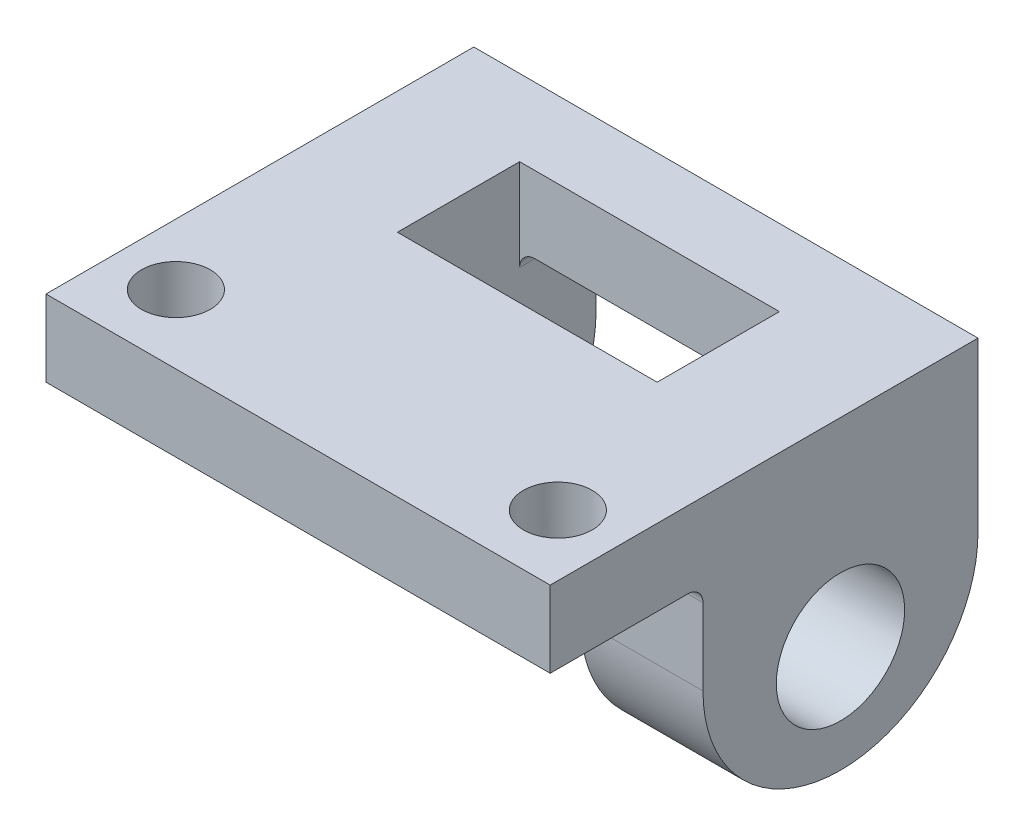
SolidWorks part; units mm, degrees
ref_plane "前视基准面" through (0, 0, 0) normal (0, 0, 1) x (1, 0, 0)
ref_plane "上视基准面" through (0, 0, 0) normal (0, 1, 0) x (1, 0, 0)
ref_plane "右视基准面" through (0, 0, 0) normal (1, 0, 0) x (0, 0, -1)
sketch "草图1" plane through (0, 0, 0) normal (0, 1, 0) x (1, 0, 0)
  line L0 (-18.5322, 0) -> (26.7717, 0) construction
  line L1 (-8.5, 4) -> (8.5, 4)
  line L2 (-8.5, 4) -> (-8.5, -4)
  line L3 (-8.5, -4) -> (8.5, -4)
  line L4 (8.5, 4) -> (8.5, -4)
  line L5 (0, 17.1481) -> (0, -22.7749) construction
  line L7 (-16.5, 9) -> (16.5, 9)
  line L8 (-16.5, 9) -> (-16.5, -19)
  line L9 (-16.5, -19) -> (16.5, -19)
  line L10 (16.5, 9) -> (16.5, -19)
  dimension "D1" = 8
  dimension "D2" = 17
  dimension "D3" = 8
  dimension "D4" = 15
  dimension "D5" = 5
extrude "凸台-拉伸1" add sketch "草图1" along normal blind 5
sketch "草图2" plane through (0, 0, 0) normal (0, -1, 0) x (1, 0, 0)
  line L0 (16.5, -9) -> (-16.5, -9) construction
  line L1 (-16.5, 9) -> (-8.5, 9)
  line L2 (-16.5, 9) -> (-16.5, -9)
  line L3 (-16.5, -9) -> (-8.5, -9)
  line L4 (-8.5, 9) -> (-8.5, -9)
  line L7 (-8.5, -4) -> (-8.5, 4) construction
  line L8 (8.5, 4) -> (8.5, -4) construction
  line L9 (16.5, 9) -> (8.5, 9)
  line L10 (16.5, 9) -> (16.5, -9)
  line L11 (16.5, -9) -> (8.5, -9)
  line L12 (8.5, 9) -> (8.5, -9)
  line L13 (-8.5, 4) -> (8.5, 4) construction
  dimension "D1" = 5
extrude "凸台-拉伸2" add sketch "草图2" along normal blind 15
sketch "草图3" plane through (-16.5, 0, 0) normal (-1, 0, 0) x (0, 0, 1)
  line L0 (-10.8871, -8) -> (13.4466, -8) construction
  line L1 (0, 4.2883) -> (0, -9.1936) construction
  line L6 (-9, 5) -> (19, 5) construction
  line L7 (4, 5) -> (4, 0) construction
  line L8 (-4, 5) -> (-4, 0) construction
  circle A0 centre (0, -8) radius 4.2
  dimension "D1" = 8.4
  dimension "D2" = 13
extrude "切除-拉伸1" cut sketch "草图3" against normal blind 37
fillet "圆角1" radius 9 4 edges at (12.5, -15, -9) (12.5, -15, 9) (-12.5, -15, 9) (-12.5, -15, -9)
fillet "圆角2" radius 1 6 edges at (8.5, 0, -6.5) (-8.5, 0, -6.5) (-12.5, 0, 9) (-8.5, 0, 6.5) (8.5, 0, 6.5) (12.5, 0, 9)
sketch "草图4" plane through (0, 0, 0) normal (0, -1, 0) x (1, 0, 0)
  line L0 (-16.5, 19) -> (16.5, 19) construction
  line L1 (16.5, 19) -> (16.5, 10) construction
  line L2 (-16.5, 10) -> (-16.5, 19) construction
  circle A0 centre (-12.5, 14.5) radius 2.25
  circle A1 centre (12.5, 14.5) radius 2.25
  dimension "D1" = 4.5
  dimension "D2" = 4.5
  dimension "D3" = 4
  dimension "D4" = 4
extrude "切除-拉伸2" cut sketch "草图4" against normal blind 37
